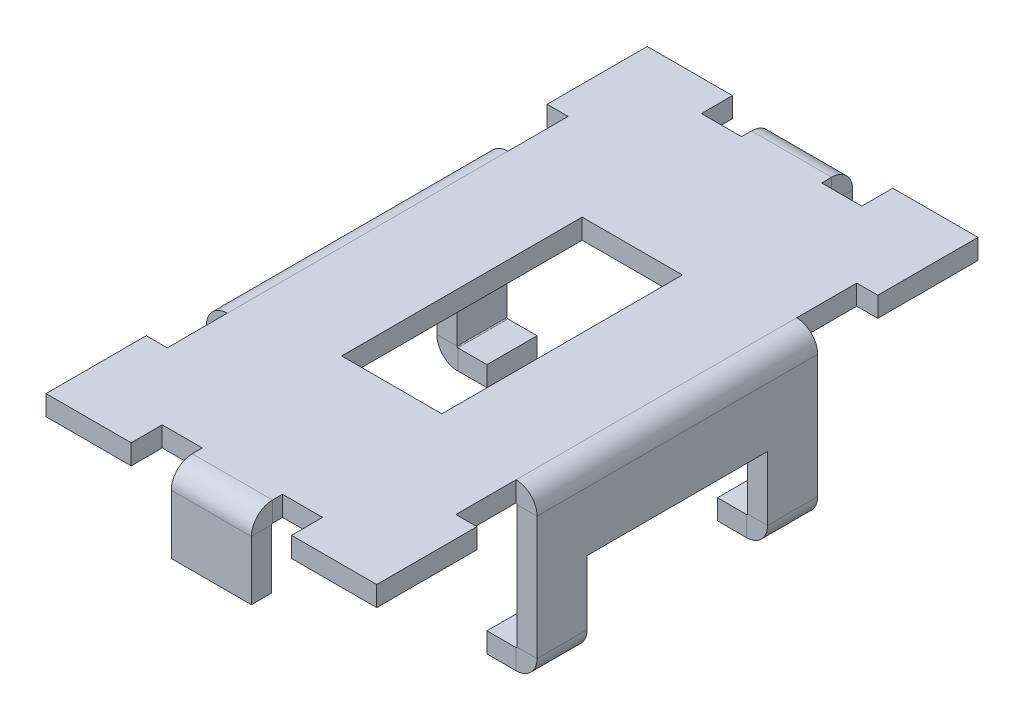
SolidWorks part; units mm, degrees
note: The reader was unsure of these and kept them because the rebuilt part matched: flange length of "Edge-Flange1", "Edge-Flange2", "Edge-Flange3".
material "201 Annealed Stainless Steel (SS)"
ref_plane "Front Plane" through (0, 0, 0) normal (0, 0, 1) x (1, 0, 0)
ref_plane "Top Plane" through (0, 0, 0) normal (0, 1, 0) x (1, 0, 0)
ref_plane "Right Plane" through (0, 0, 0) normal (1, 0, 0) x (0, 0, -1)
sketch "Sketch1" plane through (0, 0, 0) normal (0, 1, 0) x (1, 0, 0)
  line L0 (-0.9075, 0) -> (0.9075, 0) construction
  line L1 (-1.65, 3) -> (1.65, 3)
  line L2 (-1.65, 3) -> (-1.65, -3)
  line L3 (-1.65, -3) -> (1.65, -3)
  line L4 (1.65, 3) -> (1.65, -3)
  line L5 (0, -0.9075) -> (0, 0.9075) construction
  dimension "D1" = 6
  dimension "D2" = 3
  dimension "D3" = 3.3
  dimension "D4" = 1.65
sheet metal parameters "Sheet-Metal1" thickness 0.2 parameters "D1"=1.905
base flange "Base-Flange1" sketch "Sketch1" thickness 0.2 reverse thickness direction no parameters "D1"=1.905
edge flange "Edge-Flange1" sketch "Sketch6" flange profiles "Sketch6", "Sketch8" flange angle 90 flange length 0.8 flange position material inside bend radius 0.01 thickness 0.2 parameters "D6"=10, "D8"=1
sketch "Sketch6" plane through (0, -0.2, 3) normal (0, 0, 1) x (-1, 0, 0)
  line L0 (1.65, 0) -> (-1.65, 0) construction
  line L1 (0.4, 0) -> (-0.4, 0)
  line L2 (-0.4, 0) -> (-0.4, 0.6)
  line L3 (-0.4, 0.6) -> (0.4, 0.6)
  line L4 (0.4, 0.6) -> (0.4, 0)
  line L5 (0, 0.7075) -> (0, -1.1075) construction
  dimension "D1" = 0.4
  dimension "D2" = 0.8
sketch "Sketch8" plane through (0, -0.2, -3) normal (0, 0, -1) x (1, 0, 0)
  line L0 (1.65, 0) -> (-1.65, 0) construction
  line L1 (0.4, 0) -> (-0.4, 0)
  line L2 (-0.4, 0) -> (-0.4, 0.6)
  line L3 (-0.4, 0.6) -> (0.4, 0.6)
  line L4 (0.4, 0.6) -> (0.4, 0)
  line L6 (0.4, 0) -> (0.4, 0.6) construction
  line L8 (-0.4, 0.6) -> (-0.4, 0) construction
bend "EdgeBend1" bend radius 0.01 bend angle 90 parameters "D5"=1
bend "EdgeBend2" bend radius 0.01 bend angle 90 parameters "D5"=2
edge flange "Edge-Flange2" sketch "Sketch13" flange profiles "Sketch13", "Sketch14" flange angle 90 flange length 1.65 flange position material inside bend radius 0.01 thickness 0.2 parameters "D6"=10, "D8"=1
sketch "Sketch13" plane through (-1.65, -0.2, 0) normal (-1, 0, 0) x (0, 0, -1)
  line L0 (3, 0) -> (-3, 0) construction
  line L1 (1.4, 0) -> (-1.4, 0)
  line L2 (-1.4, 0) -> (-1.4, 1.45)
  line L3 (-1.4, 1.45) -> (1.4, 1.45)
  line L4 (1.4, 1.45) -> (1.4, 0)
  line L5 (0, 0.7075) -> (0, -1.1075) construction
  dimension "D1" = 1.4
  dimension "D2" = 2.8
sketch "Sketch14" plane through (1.65, -0.2, 0) normal (1, 0, 0) x (0, 0, 1)
  line L0 (3, 0) -> (-3, 0) construction
  line L1 (1.4, 0) -> (-1.4, 0)
  line L2 (-1.4, 0) -> (-1.4, 1.45)
  line L3 (-1.4, 1.45) -> (1.4, 1.45)
  line L4 (1.4, 1.45) -> (1.4, 0)
  line L5 (1.4, 0) -> (1.4, 1.45) construction
  line L6 (-1.4, 1.45) -> (-1.4, 0) construction
bend "EdgeBend3" bend radius 0.01 bend angle 90 parameters "D5"=3
bend "EdgeBend4" bend radius 0.01 bend angle 90 parameters "D5"=4
edge flange "Edge-Flange3" sketch "Sketch21" flange profiles "Sketch21", "Sketch22" flange angle 90 flange length 0.5 flange position material inside bend radius 0.01 thickness 0.2 parameters "D6"=10, "D8"=1
sketch "Sketch21" plane through (-1.45, -1.65, 0) normal (0, -1, 0) x (0, 0, -1)
  line L0 (1.4, 0) -> (-1.4, 0) construction
  line L1 (1.4, 0) -> (-1.4, 0)
  line L2 (-1.4, 0) -> (-1.4, 0.3)
  line L3 (-1.4, 0.3) -> (1.4, 0.3)
  line L4 (1.4, 0.3) -> (1.4, 0)
sketch "Sketch22" plane through (1.45, -1.65, 0) normal (0, -1, 0) x (0, 0, 1)
  line L0 (1.4, 0) -> (-1.4, 0) construction
  line L1 (1.4, 0) -> (-1.4, 0)
  line L2 (-1.4, 0) -> (-1.4, 0.3)
  line L3 (-1.4, 0.3) -> (1.4, 0.3)
  line L4 (1.4, 0.3) -> (1.4, 0)
bend "EdgeBend5" bend radius 0.01 bend angle 90 parameters "D5"=5
bend "EdgeBend6" bend radius 0.01 bend angle 90 parameters "D5"=6
sketch "Sketch23" plane through (0, 0, 0) normal (1, 0, 0) x (0, 0, -1)
  line L0 (-1.4, -1.65) -> (1.4, -1.65) construction
  line L1 (-0.9, -0.8) -> (0.9, -0.8)
  line L2 (-0.9, -0.8) -> (-0.9, -1.65)
  line L3 (-0.9, -1.65) -> (0.9, -1.65)
  line L4 (0.9, -0.8) -> (0.9, -1.65)
  line L5 (0, 0.9075) -> (0, -0.9075) construction
  line L6 (1.815, 0) -> (-1.815, 0) construction
  line L7 (-1.4, -0.21) -> (-1.4, -1.44) construction
  dimension "D1" = 1.8
  dimension "D2" = 0.9
  dimension "D3" = 0.8
  dimension "D4" = 0.5
extrude "Cut-Extrude1" cut sketch "Sketch23" against normal blind 10 and the other way blind 10
sketch "Sketch24" plane through (0, 0, 0) normal (0, 1, 0) x (1, 0, 0)
  line L1 (-0.5, -1.2) -> (0.5, -1.2)
  line L2 (-0.5, -1.2) -> (-0.5, 1.2)
  line L3 (-0.5, 1.2) -> (0.5, 1.2)
  line L4 (0.5, -1.2) -> (0.5, 1.2)
  line L5 (-0.5, -1.2) -> (0.5, 1.2) construction
  line L6 (-0.5, 1.2) -> (0.5, -1.2) construction
  point P0 (0, 0)
  dimension "D1" = 2.4
  dimension "D2" = 1
extrude "Cut-Extrude2" cut sketch "Sketch24" against normal blind 10
flat pattern "Flat-Pattern1" [suppressed]
sketch "Bend-Lines1" plane through (0, 0, 0) normal (0, 1, 0) x (1, 0, 0)
sketch3d "Bounding-Box1" [suppressed]
  line L0 (1.75, 2.35, 0) -> (1.75, -2.35, 0) construction
  line L1 (-1.75, 2.35, 0) -> (-1.75, -2.35, 0) construction
  line L2 (1.75, 2.35, 0) -> (-1.75, 2.35, 0) construction
  line L3 (1.75, -2.35, 0) -> (-1.75, -2.35, 0) construction
bend of the flat pattern "Flatten-<EdgeBend1>1"
bend of the flat pattern "Flatten-<EdgeBend2>1"
bend of the flat pattern "Flatten-<EdgeBend3>1"
bend of the flat pattern "Flatten-<EdgeBend4>1"
bend of the flat pattern "Flatten-<EdgeBend5>1"
bend of the flat pattern "Flatten-<EdgeBend6>1"
